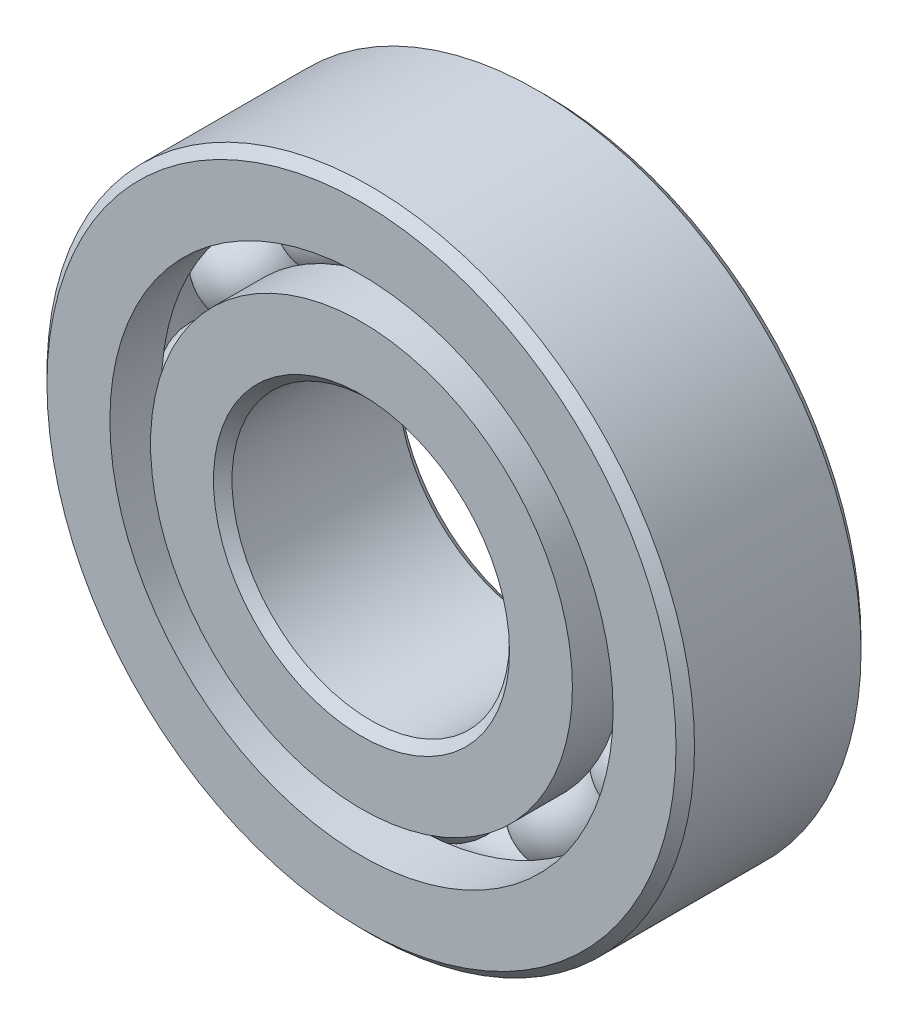
SolidWorks part; units mm, degrees
ref_plane "Front Plane" through (0, 0, 0) normal (0, 0, 1) x (1, 0, 0)
ref_plane "Top Plane" through (0, 0, 0) normal (0, 1, 0) x (1, 0, 0)
ref_plane "Right Plane" through (0, 0, 0) normal (1, 0, 0) x (0, 0, -1)
sketch "Sketch1" plane through (0, 0, 0) normal (1, 0, 0) x (0, 0, -1)
  line L0 (-4, 0) -> (4, 0) construction
  line L1 (0, 14) -> (0, -14) construction
  line L2 (3.6, 14) -> (-3.6, 14)
  line L3 (-3.6, 14) -> (-4, 13.6)
  line L4 (-4, 13.6) -> (-4, 10.8791)
  line L5 (-4, 10.8791) -> (-1.7778, 10.8791)
  line L6 (4, 10.8791) -> (1.7778, 10.8791)
  line L7 (4, 13.6) -> (4, 10.8791)
  line L8 (3.6, 14) -> (4, 13.6)
  line L9 (0, 14) -> (0, 10) construction
  line L10 (0, 10) -> (0, 6) construction
  arc A0 (-1.7778, 10.8791) -> (1.7778, 10.8791) centre (0, 10) cw
  point P14 (0, 6)
  dimension "D3" = 3.5556
  dimension "D1" = 45
  dimension "Width" = 8
  dimension "OD" = 28
  dimension "D2" = 0.4
  dimension "Shaft Dia" = 12
  dimension "D4" = 0.8791
revolve "Revolve1" add sketch "Sketch1" angle 360 about L0
sketch "Sketch3" plane through (0, 0, 0) normal (1, 0, 0) x (0, 0, -1)
  line L0 (-4, 9.1209) -> (-1.7778, 9.1209)
  line L1 (0, 14) -> (0, -14) construction
  line L2 (-4, 13.6) -> (-4, 10.8791) construction
  line L3 (-4, 9.1209) -> (-4, 6.4)
  line L4 (-3.6, 14) -> (-4, 13.6) construction
  line L5 (-4, 6.4) -> (-3.6, 6)
  line L6 (-3.6, 6) -> (3.6, 6)
  line L7 (3.6, 14) -> (3.6, -14) construction
  line L8 (3.6, 6) -> (4, 6.4)
  line L9 (4, -13.6) -> (4, 13.6) construction
  line L10 (4, 6.4) -> (4, 9.1209)
  line L11 (4, 9.1209) -> (1.7778, 9.1209)
  line L13 (3.6, 14) -> (4, 13.6) construction
  arc A0 (1.7778, 10.8791) -> (-1.7778, 10.8791) centre (0, 10) ccw construction
  arc A1 (1.7778, 9.1209) -> (-1.7778, 9.1209) centre (0, 10) cw
revolve "Revolve3" add sketch "Sketch3" angle 360 about L0
sketch "Sketch4" plane through (0, 0, 0) normal (1, 0, 0) x (0, 0, -1)
  line L0 (-1.9833, 10) -> (1.9833, 10)
  arc A2 (-1.9833, 10) -> (1.9833, 10) centre (0, 10) cw
  arc A3 (1.7778, 10.8791) -> (-1.7778, 10.8791) centre (0, 10) ccw construction
revolve "Revolve4" add sketch "Sketch4" angle 360 about L0
ref_axis "Axis1" through (0, 0, -4) along (0, 0, 1)
pattern_circular "CirPattern1" count 12 every 30 about axis through (0, 0, -4) along (0, 0, 1) of bodies 104
sketch "Sketch5" plane through (0, 0, 0) normal (1, 0, 0) x (0, 0, -1)
  line L0 (-4, 10.8791) -> (-1.7778, 10.8791) construction
  line L1 (-3.8, 10.8791) -> (-1.9833, 10.8791)
  line L2 (-3.8, 10.8791) -> (-3.8, 9.1209)
  line L3 (-3.8, 9.1209) -> (-1.9833, 9.1209)
  line L4 (-1.9833, 10.8791) -> (-1.9833, 9.1209)
  line L5 (-4, 9.1209) -> (-1.7778, 9.1209) construction
  line L6 (4, 10.8791) -> (1.7778, 10.8791) construction
  line L7 (3.8, 10.8791) -> (1.9833, 10.8791)
  line L8 (3.8, 10.8791) -> (3.8, 9.1209)
  line L9 (3.8, 9.1209) -> (1.9833, 9.1209)
  line L10 (1.9833, 10.8791) -> (1.9833, 9.1209)
  line L11 (4, 9.1209) -> (1.7778, 9.1209) construction
  line L12 (-3.6, 14) -> (-4, 13.6) construction
  point P18 (-3.8, 13.8)
equation "\"D2@Sketch1\" = \"Width@Sketch1\"*.05"
equation "\"D3@Sketch1\" = \"Width@Sketch1\"/2.25"
equation "\"D4@Sketch1\" = (((\"OD@Sketch1\"-\"Width@Sketch1\")/2)/3.25)/3.5"
equation "\"D2@CirPattern1\" = 360/\"Balls@CirPattern1\""
